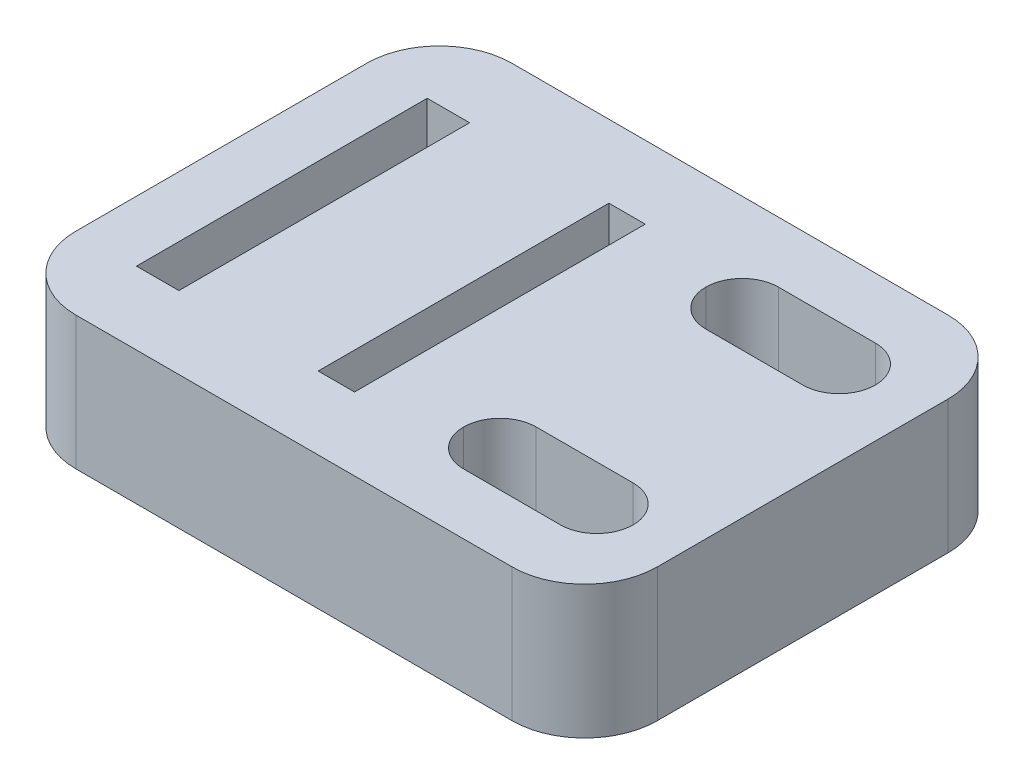
SolidWorks part; units mm, degrees
ref_plane "Front Plane" through (0, 0, 0) normal (0, 0, 1) x (1, 0, 0)
ref_plane "Top Plane" through (0, 0, 0) normal (0, 1, 0) x (1, 0, 0)
ref_plane "Right Plane" through (0, 0, 0) normal (1, 0, 0) x (0, 0, -1)
sketch "Sketch1" plane through (0, 0, 0) normal (0, 1, 0) x (1, 0, 0)
  line L1 (0, 0) -> (-24, 0)
  line L2 (0, 0) -> (0, 18)
  line L3 (0, 18) -> (-24, 18)
  line L4 (-24, 0) -> (-24, 18)
  line L5 (-14, 15) -> (-12.5, 15)
  line L6 (-14, 15) -> (-14, 3)
  line L7 (-14, 3) -> (-12.5, 3)
  line L8 (-12.5, 15) -> (-12.5, 3)
  line L9 (-21.5, 15) -> (-19.75, 15)
  line L10 (-21.5, 15) -> (-21.5, 3)
  line L11 (-21.5, 3) -> (-19.75, 3)
  line L12 (-19.75, 15) -> (-19.75, 3)
  line L13 (-9, 15.5) -> (-2, 15.5)
  line L14 (-9, 15.5) -> (-9, 12.5)
  line L15 (-9, 12.5) -> (-2, 12.5)
  line L16 (-2, 15.5) -> (-2, 12.5)
  line L17 (-9, 5.5) -> (-2, 5.5)
  line L18 (-9, 5.5) -> (-9, 2.5)
  line L19 (-9, 2.5) -> (-2, 2.5)
  line L20 (-2, 5.5) -> (-2, 2.5)
  dimension "D1" = 24
  dimension "D2" = 18
  dimension "D3" = 12
  dimension "D4" = 3
  dimension "D5" = 12
  dimension "D6" = 3
  dimension "D7" = 1.75
  dimension "D8" = 1.5
  dimension "D9" = 5.75
  dimension "D10" = 2.5
  dimension "D11" = 7
  dimension "D12" = 3
  dimension "D13" = 3
  dimension "D14" = 2.5
  dimension "D15" = 2
  dimension "D16" = 2
  dimension "D17" = 7
  dimension "D18" = 7
extrude "Boss-Extrude1" add sketch "Sketch1" along normal blind 5.5
fillet "Fillet1" radius 3 1 edges at (0, 2.75, 0)
fillet "Fillet2" radius 3 3 edges at (-24, 2.75, 0) (-24, 2.75, -18) (0, 2.75, -18)
fillet "Fillet4" radius 1.5 5 edges at (-9, 2.75, -15.5) (-9, 2.75, -5.5) (-9, 2.75, -12.5) (-9, 2.75, -2.5) (-2, 2.75, -2.5)
fillet "Fillet5" radius 1.5 3 edges at (-2, 2.75, -12.5) (-2, 2.75, -5.5) (-2, 2.75, -15.5)
